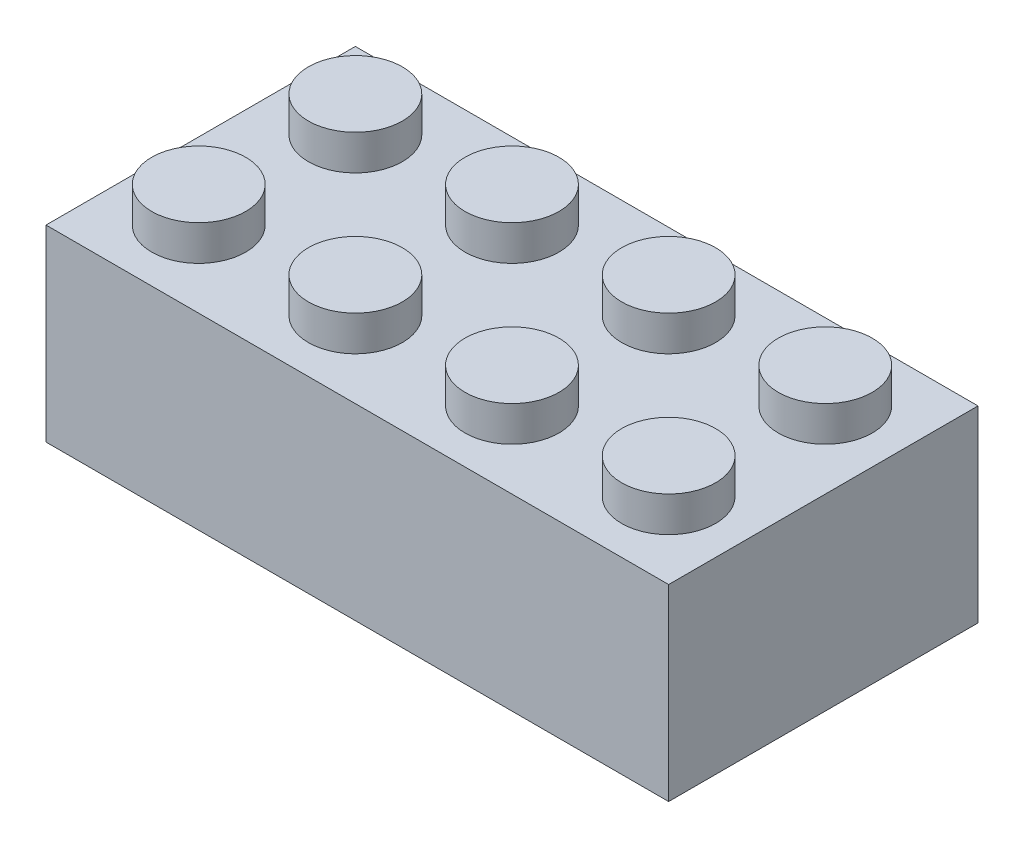
SolidWorks part; units mm, degrees
material "ABS"
ref_plane "Front Plane" through (0, 0, 0) normal (0, 0, 1) x (1, 0, 0)
ref_plane "Top Plane" through (0, 0, 0) normal (0, 1, 0) x (1, 0, 0)
ref_plane "Right Plane" through (0, 0, 0) normal (1, 0, 0) x (0, 0, -1)
sketch "Sketch1" plane through (0, 0, 0) normal (0, 1, 0) x (1, 0, 0)
  line L0 (-14.7, 6.7) -> (-12.6, 6.7)
  line L1 (-15.9, 7.9) -> (15.9, 7.9)
  line L2 (-15.9, 7.9) -> (-15.9, -7.9)
  line L3 (-15.9, -7.9) -> (15.9, -7.9)
  line L4 (15.9, 7.9) -> (15.9, -7.9)
  line L5 (-15.9, 7.9) -> (15.9, -7.9) construction
  line L6 (-15.9, -7.9) -> (15.9, 7.9) construction
  line L7 (-12.6, 6.7) -> (-12.6, 6.5)
  line L8 (-12.6, 6.5) -> (-11.4, 6.5)
  line L9 (-11.4, 6.5) -> (-11.4, 6.7)
  line L10 (-11.4, 6.7) -> (-8, 6.7)
  line L11 (-3.4, 6.5) -> (-3.4, 6.7)
  line L12 (-4.6, 6.7) -> (-4.6, 6.5)
  line L13 (-4.6, 6.5) -> (-3.4, 6.5)
  line L14 (4.6, 6.5) -> (4.6, 6.7)
  line L15 (3.4, 6.7) -> (3.4, 6.5)
  line L16 (3.4, 6.5) -> (4.6, 6.5)
  line L17 (12.6, 6.5) -> (12.6, 6.7)
  line L18 (11.4, 6.7) -> (11.4, 6.5)
  line L19 (11.4, 6.5) -> (12.6, 6.5)
  line L20 (-8, 6.7) -> (-4.6, 6.7)
  line L21 (-3.4, 6.7) -> (3.4, 6.7)
  line L22 (4.6, 6.7) -> (11.4, 6.7)
  line L23 (-14.7, 6.7) -> (-14.7, 4.6)
  line L24 (-14.7, 4.6) -> (-14.5, 4.6)
  line L25 (-14.5, 4.6) -> (-14.5, 3.4)
  line L26 (-14.5, 3.4) -> (-14.7, 3.4)
  line L27 (-14.7, 3.4) -> (-14.7, -3.4)
  line L28 (0, 7.9) -> (0, -7.9) construction
  line L29 (14.7, 6.7) -> (12.6, 6.7)
  line L30 (14.7, 3.4) -> (14.7, -3.4)
  line L31 (14.5, 3.4) -> (14.7, 3.4)
  line L32 (14.5, 4.6) -> (14.5, 3.4)
  line L33 (14.7, 4.6) -> (14.5, 4.6)
  line L34 (14.7, 6.7) -> (14.7, 4.6)
  line L35 (0, 0) -> (15.9, 0) construction
  line L36 (14.7, -6.7) -> (14.7, -4.6)
  line L37 (14.7, -4.6) -> (14.5, -4.6)
  line L38 (14.5, -4.6) -> (14.5, -3.4)
  line L39 (14.5, -3.4) -> (14.7, -3.4)
  line L40 (14.7, -6.7) -> (12.6, -6.7)
  line L41 (-14.5, -3.4) -> (-14.7, -3.4)
  line L42 (-14.5, -4.6) -> (-14.5, -3.4)
  line L43 (-14.7, -4.6) -> (-14.5, -4.6)
  line L44 (-14.7, -6.7) -> (-14.7, -4.6)
  line L45 (4.6, -6.7) -> (11.4, -6.7)
  line L46 (-3.4, -6.7) -> (3.4, -6.7)
  line L47 (-8, -6.7) -> (-4.6, -6.7)
  line L48 (11.4, -6.5) -> (12.6, -6.5)
  line L49 (11.4, -6.7) -> (11.4, -6.5)
  line L50 (12.6, -6.5) -> (12.6, -6.7)
  line L51 (3.4, -6.5) -> (4.6, -6.5)
  line L52 (3.4, -6.7) -> (3.4, -6.5)
  line L53 (4.6, -6.5) -> (4.6, -6.7)
  line L54 (-4.6, -6.5) -> (-3.4, -6.5)
  line L55 (-4.6, -6.7) -> (-4.6, -6.5)
  line L56 (-3.4, -6.5) -> (-3.4, -6.7)
  line L57 (-11.4, -6.7) -> (-8, -6.7)
  line L58 (-11.4, -6.5) -> (-11.4, -6.7)
  line L59 (-12.6, -6.5) -> (-11.4, -6.5)
  line L60 (-12.6, -6.7) -> (-12.6, -6.5)
  line L61 (-14.7, -6.7) -> (-12.6, -6.7)
  line L62 (-12, 6.5) -> (-12, -6.5) construction
  line L63 (-14.5, 4) -> (14.5, 4) construction
  circle A0 centre (-8, 0) radius 3.25
  circle A1 centre (-12, 4) radius 1.3
  circle A2 centre (12, 4) radius 1.3
  circle A3 centre (12, -4) radius 1.3
  circle A4 centre (-12, -4) radius 1.3
  circle A5 centre (0, 0) radius 3.25
  circle A7 centre (8, 0) radius 3.25
  circle A8 centre (-8, 0) radius 2.05
  circle A9 centre (0, 0) radius 2.05
  circle A10 centre (8, 0) radius 2.05
  point P0 (0, 0)
  point P16 (-12, 6.5)
  point P47 (14.7, 0)
  point P49 (-14.7, 0)
  dimension "D7" = 6.5
  dimension "D11" = 2.6
  dimension "D12" = 1.2
  dimension "D1" = 31.8
  dimension "D2" = 15.8
  dimension "D3" = 1.2
  dimension "D4" = 1.2
  dimension "D5" = 0.2
  dimension "D6" = 1.2
  dimension "D8" = 8
  dimension "D9" = 4
  dimension "D10" = 4
extrude "Boss-Extrude1" add sketch "Sketch1" along normal blind 9.6 contours L1 L4 L3 L2
sketch "Sketch2" plane through (0, 9.6, 0) normal (0, 1, 0) x (1, 0, 0)
  circle A0 centre (-12, 4) radius 2.4
  circle A1 centre (-4, 4) radius 2.4
  circle A2 centre (4, 4) radius 2.4
  circle A3 centre (12, 4) radius 2.4
  circle A4 centre (-4, -4) radius 2.4
  circle A5 centre (4, -4) radius 2.4
  circle A6 centre (12, -4) radius 2.4
  circle A7 centre (-12, -4) radius 2.4
  point P2 (0, 0)
  point P4 (0, 0)
  point P5 (0, 0)
  point P20 (0, 0)
  point P21 (0, 0)
  point P22 (0, 0)
  dimension "D3" = 4.8
  dimension "D1" = 12
  dimension "D2" = 4
  dimension "D6" = 8
  dimension "D7" = 8
  dimension "D4" = 4
  dimension "D5" = 2
extrude "Boss-Extrude2" add sketch "Sketch2" along normal blind 1.8
extrude "Cut-Extrude3" cut sketch "Sketch1<5>" along normal blind 8.6 contours L57 L47 L55 L54 L56 L46 L52 L51 L53 L45 L49 L48 L50 L40 L36 L37 L38 L39 L30 L31 L32 L33 L34 L29 L17 L19 L18 L22 L14 L16 L15 L21 L11 L13 L12 L20 L10 L9 L8 L7 L0 L23 L24 L25 L26 L27 L41 L42 L43 L44 L61 L60 L59 L58 | A0 | A8 | A5 | A9 | A10 | A7
sketch "Sketch1<5>" plane through (0, 0, 0) normal (0, 1, 0) x (1, 0, 0) same geometry as "Sketch1"
extrude "Cut-Extrude4" cut sketch "Sketch1<6>" along normal offset from surface (10.3 mm away) 1.1 contours A4 | A1 | A3 | A2 region at (-12, 0, -4) region at (12, 0, -4) region at (12, 0, 4) region at (-12, 0, 4) up to face at (-12, 11.4, 6.4)
sketch "Sketch1<6>" plane through (0, 0, 0) normal (0, 1, 0) x (1, 0, 0) same geometry as "Sketch1"
sketch "Sketch3" plane through (0, 8.6, 0) normal (0, -1, 0) x (1, 0, 0)
  line L0 (-0.55, 3.2031) -> (-0.55, 6.7)
  line L1 (-3.4, 6.7) -> (3.4, 6.7) construction
  line L2 (0.55, 3.2031) -> (0.55, 6.7)
  line L3 (-3.4, 6.7) -> (3.4, 6.7) construction
  line L4 (-0.55, 3.2031) -> (0.55, 3.2031)
  line L5 (-0.55, 6.7) -> (0.55, 6.7)
  circle A0 centre (0, 0) radius 3.25 construction
  dimension "D1" = 1.1
extrude "Boss-Extrude3" add sketch "Sketch3" along normal offset from surface (6.3 mm away) 2.3 up to face at (0, 0, 3.25)
pattern_linear "LPattern2" count 3 spacing 8 along (1, 0, 0) of face at (-12, 10.3, 5.3) of face at (-12, 10.3, -2.7) of face at (-12, 10.3, 5.3) of face at (-12, 10.3, -2.7)
mirror "Mirror1" about plane through (0, 0, 0) normal (0, 0, 1) of "Boss-Extrude3"
